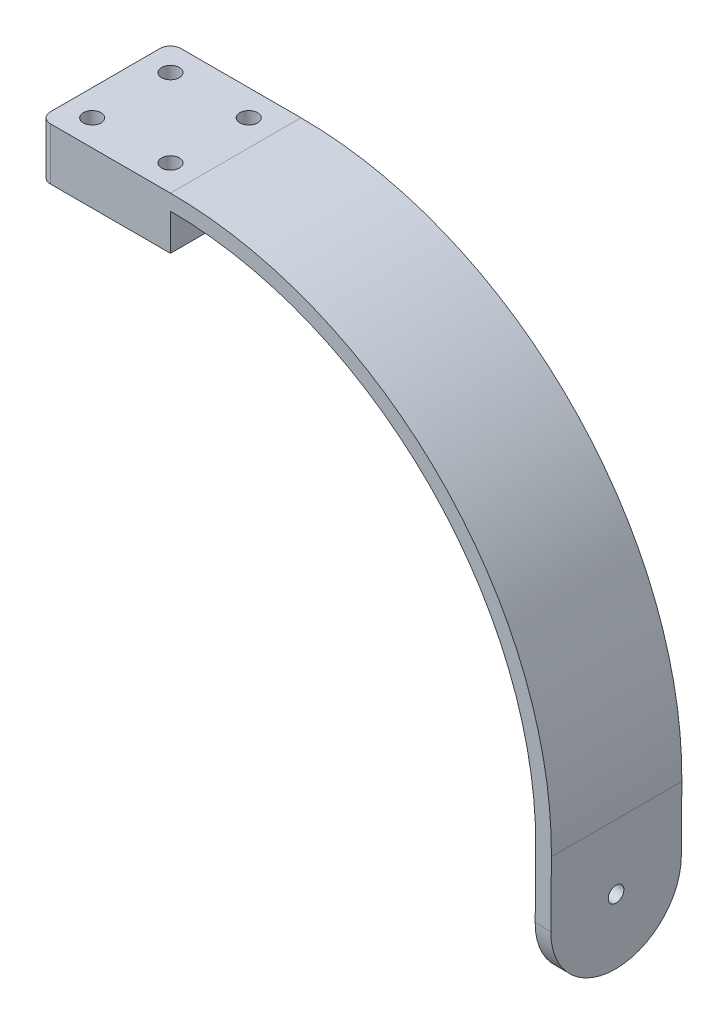
SolidWorks part; units mm, degrees
ref_plane "Front Plane" through (0, 0, 0) normal (0, 0, 1) x (1, 0, 0)
ref_plane "Top Plane" through (0, 0, 0) normal (0, 1, 0) x (1, 0, 0)
ref_plane "Right Plane" through (0, 0, 0) normal (1, 0, 0) x (0, 0, -1)
sketch "Sketch2" plane through (0, 0, 0) normal (0, 0, 1) x (1, 0, 0)
  line L0 (0, 0) -> (0, 70) construction
  line L1 (0, 0) -> (69.9973, -0.6109) construction
  line L4 (0, 73) -> (-25, 73)
  line L5 (-25, 73) -> (-25, 70)
  line L6 (-25, 70) -> (0, 70)
  line L7 (69.9973, -0.6109) -> (69.7792, -25.6099)
  line L8 (69.7792, -25.6099) -> (72.7791, -25.6361)
  line L9 (72.7791, -25.6361) -> (72.9972, -0.637)
  arc A0 (0, 70) -> (69.9973, -0.6109) centre (0, 0) cw
  arc A1 (0, 73) -> (72.9972, -0.637) centre (0, 0) cw
  dimension "D2" = 70
  dimension "D1" = 90.5
  dimension "D3" = 3
  dimension "D4" = 25
  dimension "D5" = 25
extrude "Boss-Extrude1" add sketch "Sketch2" along normal blind 25
sketch "Sketch3" plane through (0, 73, 0) normal (0, 1, 0) x (1, 0, 0)
  line L0 (-25, -23) -> (-25, -2) construction
  line L1 (-20, -5) -> (-5, -5) construction
  line L2 (-20, -5) -> (-20, -20) construction
  line L3 (-20, -20) -> (-5, -20) construction
  line L4 (-5, -5) -> (-5, -20) construction
  line L5 (-20, -5) -> (-5, -20) construction
  line L6 (-20, -20) -> (-5, -5) construction
  line L7 (0, -25) -> (-23, -25) construction
  line L8 (0, 0) -> (-23, 0) construction
  point P0 (-20, -5)
  point P1 (-5, -20)
  point P2 (-20, -20)
  point P3 (-5, -5)
  point P4 (-12.5, -12.5)
  dimension "D1" = 5
  dimension "D2" = 5
  dimension "D3" = 5
sketch "Sketch6" plane through (72.9972, -0.637, 0) normal (1, -0.0087, 0) x (0, 0, -1)
  line L1 (-25, 0) -> (0, -25) construction
  line L4 (0, 0) -> (-25, -25) construction
  circle A1 centre (-12.5, -12.5) radius 1.5
  dimension "D1" = 3
extrude "Cut-Extrude1" cut sketch "Sketch6" against normal up to next
fillet "Fillet1" radius 12.5 2 edges at (71.2791, -25.623, 0) (71.2791, -25.623, 25)
sketch "Sketch8" plane through (0, 70, 0) normal (0, -1, 0) x (1, 0, 0)
  line L1 (-25, 25) -> (0, 25)
  line L2 (-25, 25) -> (-25, 0)
  line L3 (-25, 0) -> (0, 0)
  line L4 (0, 25) -> (0, 0)
  line L5 (-25, 25) -> (0, 0) construction
  line L6 (-25, 0) -> (0, 25) construction
  point P4 (-12.5, 12.5)
extrude "Boss-Extrude2" add sketch "Sketch8" along normal blind 7
fillet "Fillet2" radius 2 2 edges at (-25, 68, 25) (-25, 68, 0)
hole_wizard "M3 Clearance Hole1" positions "Sketch3" profile "Sketch5" hole size "M3" standard "ANSI Metric"
sketch "Sketch5" plane through (-20, 73, 5) normal (1, 0, 0) x (0, 0, 1)
  line L0 (0, 0) -> (0, 98.6361)
  line L1 (0, 98.6361) -> (1.7, 98.6361)
  line L2 (1.7, 98.6361) -> (1.7, 0)
  line L5 (1.7, 0) -> (0, 0)
  line L11 (0, -6.35) -> (0, 107.95) construction
  dimension "Thru Hole Dia." = 3.4
  dimension "Thru Hole Depth" = 98.6361
equation "\"D1@Sketch2\"=362/4"
equation "\"D2@Sketch3\"=\"D1@Sketch3\""
equation "\"D3@Sketch3\"=\"D1@Sketch3\""
